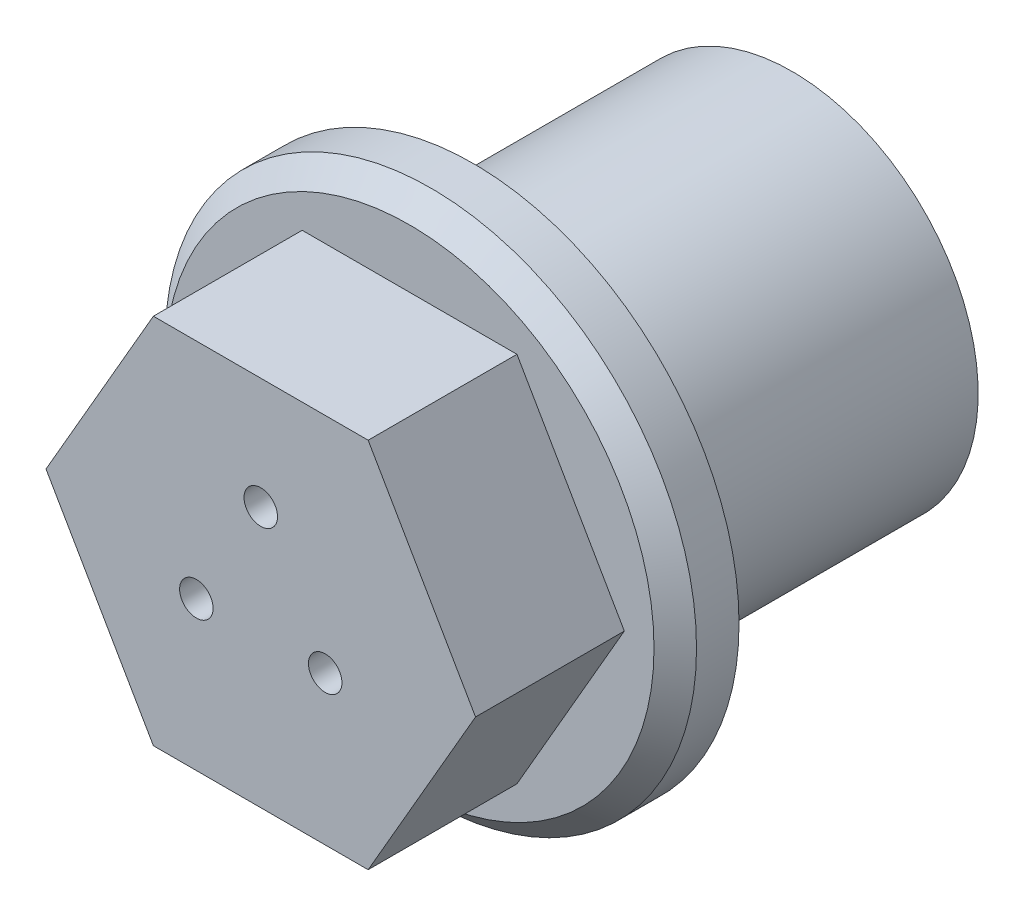
SolidWorks part; units mm, degrees
ref_plane "Front" through (0, 0, 0) normal (0, 0, 1) x (1, 0, 0)
ref_plane "Top" through (0, 0, 0) normal (0, 1, 0) x (1, 0, 0)
ref_plane "Right" through (0, 0, 0) normal (1, 0, 0) x (0, 0, -1)
sketch "Sketch1" plane through (0, 0, 0) normal (0, 0, 1) x (1, 0, 0)
  circle A0 centre (0, 0) radius 11.1125
  dimension "D1" = 22.225
extrude "Boss-Extrude1" add sketch "Sketch1" along normal blind 19.05
sketch "Sketch2" plane through (0, 0, 19.05) normal (0, 0, 1) x (1, 0, 0)
  circle A0 centre (0, 0) radius 15.875
  dimension "D1" = 31.75
extrude "Boss-Extrude2" add sketch "Sketch2" along normal blind 12.7
sketch "Sketch3" plane through (0, 0, 31.75) normal (0, 0, 1) x (1, 0, 0)
  line L1 (12.8316, 0) -> (6.4158, 11.1125)
  line L2 (6.4158, 11.1125) -> (-6.4158, 11.1125)
  line L3 (-6.4158, 11.1125) -> (-12.8316, 0)
  line L4 (-12.8316, 0) -> (-6.4158, -11.1125)
  line L5 (-6.4158, -11.1125) -> (6.4158, -11.1125)
  line L6 (6.4158, -11.1125) -> (12.8316, 0)
  circle A0 centre (0, 0) radius 11.1125 construction
  circle A2 centre (0, 0) radius 15.875
  circle A3 centre (0, 0) radius 15.875
  dimension "D1" = 22.225
  dimension "D2" = 0
extrude "Cut-Extrude1" cut sketch "Sketch3" against normal blind 8.89
chamfer "Chamfer1" distance 1.27 angle 45 1 edges at (15.875, 0, 22.86)
sketch "Sketch4" plane through (0, 0, 31.75) normal (0, 0, 1) x (1, 0, 0)
  circle A0 centre (0, 0) radius 4.445 construction
  circle A1 centre (0, 4.445) radius 1
  circle A2 centre (3.8495, -2.2225) radius 1
  circle A3 centre (-3.8495, -2.2225) radius 1
  point P11 (0, 0)
  dimension "D1" = 8.89
  dimension "D2" = 2
  dimension "D3" = 3
sketch "Sketch5" plane through (0, 0, 22.86) normal (0, 0, 1) x (1, 0, 0)
  circle A0 centre (0, 0) radius 5.445
sketch "Sketch6" plane through (0, 0, 0) normal (0, 0, -1) x (-1, 0, 0)
  circle A0 centre (0, 0) radius 9.5504
  dimension "D1" = 19.1008
loft "Cut-Loft1" cut profiles "Sketch6", "Sketch5" connector at (2.3518, 9.2563, 0) connector at (2.6441, 4.7599, 22.86)
extrude "Cut-Extrude2" cut sketch "Sketch4" against normal up to next
